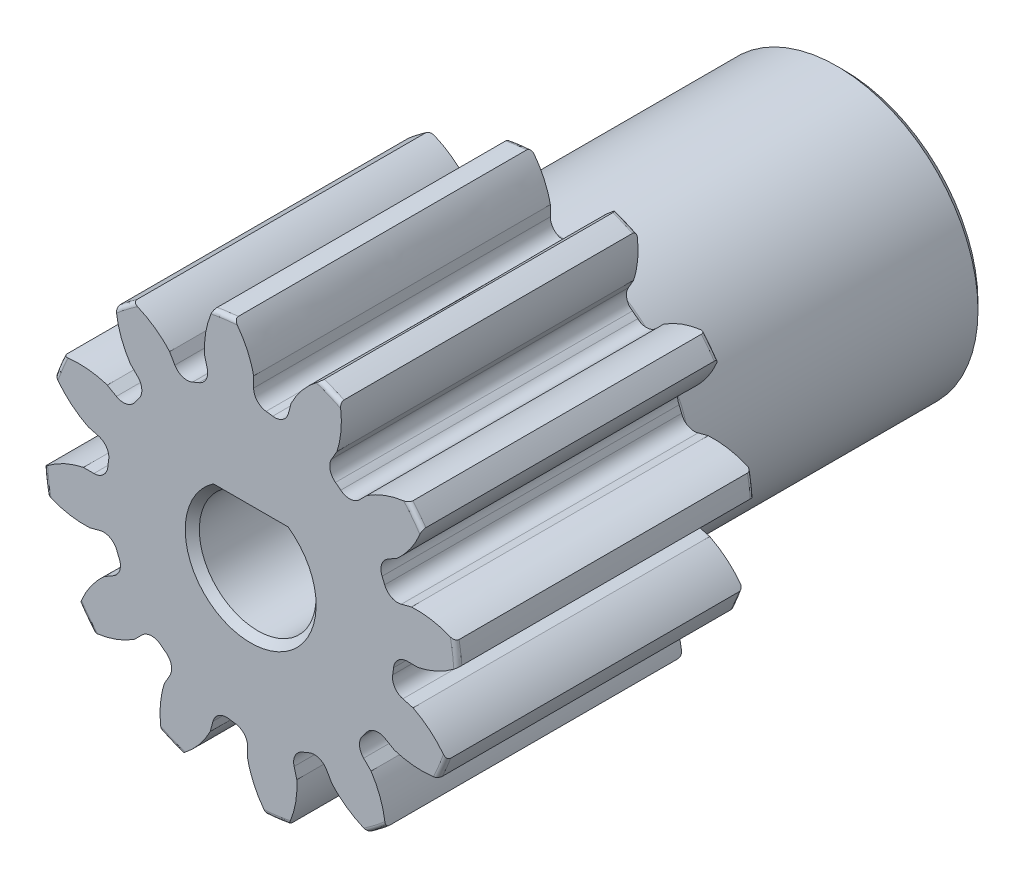
SolidWorks part; units mm, degrees
material "PLA Yellow"
ref_plane "Front" through (0, 0, 0) normal (0, 0, 1) x (1, 0, 0)
ref_plane "Top" through (0, 0, 0) normal (0, 1, 0) x (1, 0, 0)
ref_plane "Right" through (0, 0, 0) normal (1, 0, 0) x (0, 0, -1)
sketch "Sketch1" plane through (0, 0, 0) normal (0, 0, 1) x (1, 0, 0)
  line L0 (-152.4, 0) -> (152.4, 0) construction
  circle A0 centre (0, 0) radius 8.89
  circle A1 centre (0, 0) radius 7.62 construction
  circle A3 centre (0, 0) radius 6.1506 construction
  dimension "D1" = 1.4694
  dimension "D2" = 2.7394
  dimension "D3" = 1.27
extrude "Boss-Extrude1" add sketch "Sketch1" against normal blind 12.7
sketch "Sketch2" plane through (0, 0, 0) normal (1, 0, 0) x (0, 0, -1)
  line L0 (12.7, 0) -> (25.4, 0)
  line L1 (12.7, 0) -> (12.7, 6.0325)
  line L2 (12.7, 6.0325) -> (25.4, 6.0325)
  line L3 (25.4, 6.0325) -> (25.4, 0)
  point P5 (25.4, -6.0325)
  point P6 (0, -8.89)
  point P7 (12.7, -8.89)
  point P9 (0, 8.89)
revolve "Revolve1" add sketch "Sketch2" angle 360 mid plane about L0
fillet "Fillet2" radius 0.1778 3 edges at (8.89, 0, -12.7) (8.89, 0, 0) (6.0325, 0, -12.7)
sketch "Sketch3" plane through (0, 0, 0) normal (0, 0, 1) x (1, 0, 0)
  line L0 (0, 0) -> (0, 8.89) construction
  line L1 (-2.449, 6.7286) -> (0, 7.62)
  line L2 (-9.5921, 7.62) -> (9.5921, 7.62) construction
  line L3 (-9.0136, 4.3393) -> (9.0136, 10.9007) construction
  line L4 (-2.449, 6.7286) -> (0, 0) construction
  line L5 (-5.9706, 3.9527) -> (0, 0) construction
  line L6 (-5.9706, 3.9527) -> (-2.0143, 9.9288) construction
  line L7 (-1.7012, 6.9554) -> (0, 0) construction
  line L8 (-1.7012, 6.9554) -> (0.0709, 7.3889) construction
  arc A0 (-2.449, 6.7286) -> (-5.9706, 3.9527) centre (0, 0) ccw
  circle A1 centre (0, 0) radius 7.62 construction
  circle A2 centre (0, 0) radius 7.1605 construction
  arc A3 (-2.449, 6.7286) -> (-1.7012, 6.9554) centre (0, 0) cw
  circle A4 centre (0, 0) radius 8.89 construction
  point P6 (0, 7.62)
  dimension "D1" = 2.6062
  dimension "D3" = 7.167
  dimension "D5" = 1.8243
  dimension "D2" = 4.5608
  dimension "D4" = 0.7819
sketch "Sketch4" plane through (0, 0, 0) normal (0, 0, 1) x (1, 0, 0)
  line L0 (0, 0) -> (0.9861, 7.4902) construction
  line L1 (0.1265, 7.1593) -> (0.1265, 6.1493)
  line L2 (0, 7.62) -> (1.9722, 7.3604) construction
  line L3 (1.7308, 6.9481) -> (1.4694, 5.9725)
  line L4 (0.1265, 6.1493) -> (0, 0) construction
  line L5 (0, 0) -> (0, 8.89) construction
  line L6 (-5.9706, 3.9527) -> (-2.0143, 9.9288) construction
  line L7 (-5.9706, 3.9527) -> (-2.0143, 9.9288) construction
  arc A0 (1.4694, 5.9725) -> (0.1265, 6.1493) centre (0, 0) ccw
  arc A1 (0, 7.62) -> (1.9722, 7.3604) centre (0, 0) cw construction
  circle A2 centre (0, 0) radius 7.62 construction
  circle A3 centre (0, 0) radius 7.1605 construction
  circle A4 centre (0, 0) radius 6.1506 construction
  arc A5 (4.5154, 9.0691) -> (-2.0143, 9.9288) centre (0, 0) ccw
  spline S0 degree 2 poles (-2.0143, 9.9288) (-0.2409, 8.8946) (0.1265, 7.1593) knots 0 0 0 1 1 1
  spline S1 degree 2 poles (4.5154, 9.0691) (2.5348, 8.5291) (1.7308, 6.9481) knots 0 0 0 1 1 1
  dimension "D1" = 1.9949
extrude "Cut-Extrude1" cut sketch "Sketch4" against normal through all
fillet "Fillet1" radius 0.5985 2 edges at (1.4694, 5.9725, -6.3552) (0.1265, 6.1493, -6.3552)
pattern_circular "CirPattern1" count 12 over 360 about axis through (0, 0, -12.7) along (0, 0, 1) of "Cut-Extrude1", "Fillet1"
sketch "Sketch5" plane through (0, 0, 0) normal (0, 0, 1) x (1, 0, 0)
  line L0 (-1.5, 2) -> (1.5, 2)
  circle A0 centre (0, 0) radius 2.5
  circle A1 centre (0, 0) radius 2.5 construction
  point P6 (0, 2.5)
  dimension "D1" = 0.5
  dimension "Bore Min" = 5
  dimension "Bore Max" = 5
extrude "Cut-Extrude2" cut sketch "Sketch5" against normal through all contours L0 A0 region at (0, -0.1209, 0)
chamfer "Chamfer1" distance 0.3016 angle 45 5 edges at (6.0325, 0, -25.4) (0, -2.5, 0) (0, -2.5, -25.4) (0, 2, -25.4) (0, 2, 0)
sketch "Pitch Dia" plane through (0, 0, 0) normal (0, 0, 1) x (1, 0, 0)
  circle A0 centre (0, 0) radius 7.62 construction
  circle A1 centre (0, 0) radius 7.62 construction
equation "\"D1@Boss-Extrude1\" = \"Face Wd@Sketch2\""
equation "\"D2@Sketch3\" = \"D1@Sketch3\"*1.75"
equation "\"D3@Sketch3\" = \"D1@Sketch3\"+\"D2@Sketch3\""
equation "\"D4@Sketch3\" = \"D1@Sketch3\"*.3"
equation "\"D5@Sketch3\" = \"D1@Sketch3\"-\"D4@Sketch3\""
equation "\"D1@Sketch4\" = 1.5708/(\"Number of Teeth@Sketch1\"/\"Ptich Dia@Sketch1\")"
equation "\"D1@Chamfer1\" = \"B Hub Dia@Sketch2\"*.025"
equation "\"D1@CirPattern1\" = \"Number of Teeth@Sketch1\""
equation "\"D1@Fillet1\" = \"D1@Sketch4\"*.3"
equation "\"D1@Fillet2\" = \"OD@Sketch1\"*.01"
equation "\"D1@Sketch1\" = 1.157/(\"Number of Teeth@Sketch1\"/\"Ptich Dia@Sketch1\")"
